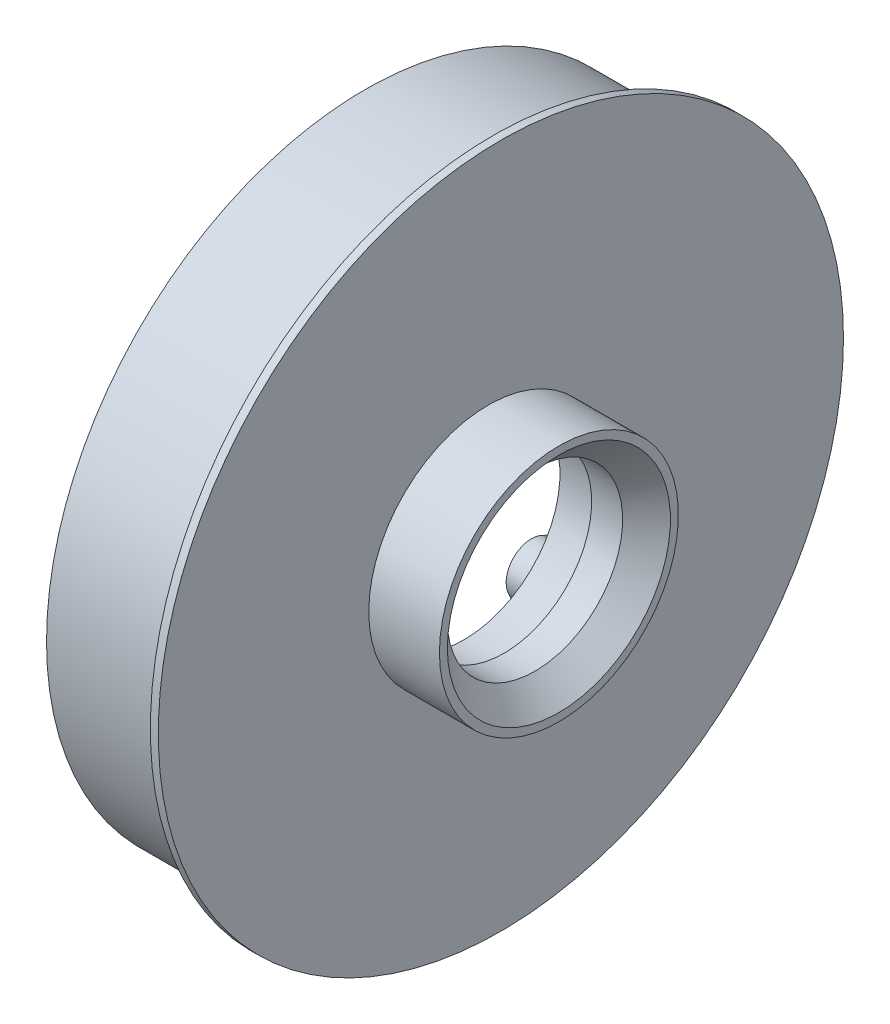
SolidWorks part; units mm, degrees
ref_plane "Front Plane" through (0, 0, 0) normal (0, 0, 1) x (1, 0, 0)
ref_plane "Top Plane" through (0, 0, 0) normal (0, 1, 0) x (1, 0, 0)
ref_plane "Right Plane" through (0, 0, 0) normal (1, 0, 0) x (0, 0, -1)
sketch "Sketch2" plane through (0, 0, 0) normal (0, 0, 1) x (1, 0, 0)
  line L0 (0, 0) -> (58.591, 0) construction
  line L2 (0, 0) -> (18.4, 0)
  line L3 (0, 0) -> (0, 2.5)
  line L4 (0, 2.5) -> (18.4, 2.5)
  line L5 (18.4, 0) -> (18.4, 2.5)
  line L6 (6, 2.5) -> (6, 6)
  line L11 (6, 6) -> (9.97, 6)
  line L16 (12.97, 6) -> (12.97, 3)
  line L17 (12.97, 3) -> (13.6304, 3)
  line L18 (13.6304, 3) -> (13.6304, 2.5)
  line L19 (13.6304, 2.5) -> (6, 2.5)
  line L22 (13.6304, 2.5) -> (16.1104, 2.5)
  line L23 (13.6304, 2.5) -> (13.6304, 4)
  line L24 (13.6304, 4) -> (16.1104, 4)
  line L25 (16.1104, 2.5) -> (16.1104, 4)
  line L27 (6, 6) -> (9.97, 6)
  line L28 (6, 6) -> (6, 9)
  line L29 (6, 9) -> (9.97, 9)
  line L30 (9.97, 6) -> (9.97, 9)
  line L31 (6, 9) -> (6, 8.25)
  line L32 (6, 8.25) -> (5, 8.25)
  line L33 (8.58, 22.001) -> (8.58, 12.476) construction
  line L34 (5, 12.476) -> (12.16, 12.476)
  line L35 (9.97, 9) -> (12.16, 9)
  line L36 (5, 7.5) -> (3, 7.5)
  line L37 (5, 8.25) -> (5, 12.476)
  line L38 (5, 7.5) -> (5, 14)
  line L39 (5, 14) -> (3, 14)
  line L40 (3, 7.5) -> (3, 14)
  line L41 (5, 22.001) -> (12.16, 22.001)
  line L42 (5, 22.001) -> (5, 30.1625)
  line L43 (5, 30.1625) -> (12.16, 30.1625)
  line L44 (12.16, 22.001) -> (12.16, 30.1625)
  line L49 (16.6304, 22.001) -> (16.6304, 7.5)
  line L51 (23.0104, 7.5) -> (23.0104, 6.5)
  line L54 (16.1104, 4) -> (13.6304, 4)
  line L56 (18.0304, 7.5) -> (23.0104, 7.5)
  line L57 (13.16, 22.001) -> (16.6304, 22.001)
  line L58 (16.1104, 3.5) -> (20.0104, 3.5)
  line L59 (29.9004, 14) -> (26.9004, 11)
  line L60 (4, 31.75) -> (18.0304, 31.75)
  line L61 (18.0304, 7.5) -> (23.0104, 7.5)
  line L62 (18.0304, 7.5) -> (18.0304, 12)
  line L63 (18.0304, 12) -> (23.0104, 12)
  line L64 (23.0104, 7.5) -> (23.0104, 12)
  line L65 (18.0304, 31.75) -> (18.0304, 12)
  line L66 (23.0104, 11) -> (26.9004, 11)
  line L67 (34.8004, 23) -> (31.3004, 19.5)
  line L68 (35.8004, 31) -> (38.7904, 33.99)
  line L69 (29.9004, 14) -> (29.9004, 15)
  line L70 (29.9004, 15) -> (22.9304, 15)
  line L71 (22.9304, 15) -> (21.0304, 15)
  line L72 (18.0304, 7.5) -> (16.6304, 7.5)
  line L73 (21.0304, 15) -> (21.0304, 43)
  line L74 (20.0304, 40) -> (10.0704, 40)
  line L75 (10.0704, 40) -> (4, 40)
  line L76 (21.0304, 43) -> (20.0304, 43)
  line L77 (22.9304, 15) -> (29.9004, 15)
  line L78 (22.9304, 15) -> (22.9304, 21)
  line L79 (22.9304, 21) -> (29.9004, 21)
  line L80 (29.9004, 15) -> (29.9004, 21)
  line L81 (10.0704, 40) -> (20.0304, 40)
  line L82 (10.0704, 40) -> (10.0704, 50)
  line L83 (10.0704, 50) -> (20.0304, 50)
  line L84 (20.0304, 40) -> (20.0304, 50)
  line L85 (4, 40) -> (4, 31.75)
  line L86 (12.97, 3) -> (12.97, 2.5)
  line L87 (31.3004, 19.5) -> (29.9004, 19.5)
  line L88 (21.51, 63.5) -> (21.51, 44)
  line L89 (21.51, 63.5) -> (25.9304, 63.5)
  line L90 (25.9304, 63.5) -> (25.9304, 25)
  line L91 (27.8304, 25) -> (25.9304, 25)
  line L92 (10.0704, 48) -> (9, 48)
  line L93 (9, 48) -> (9, 53.476)
  line L94 (9, 53.476) -> (20.0304, 53.476)
  line L95 (20.0304, 53.476) -> (20.0304, 50)
  line L96 (14.5152, 63.001) -> (14.5152, 53.476) construction
  line L97 (9, 63.001) -> (20.0304, 63.001)
  line L98 (9, 63.001) -> (9, 68.2625)
  line L99 (9, 68.2625) -> (20.0304, 68.2625)
  line L100 (20.0304, 63.001) -> (20.0304, 68.2625)
  line L101 (12.97, 6) -> (11.97, 6)
  line L102 (9, 42.5) -> (5, 42.5)
  line L103 (9, 42.5) -> (9, 55)
  line L104 (9, 55) -> (5, 55)
  line L105 (5, 42.5) -> (5, 55)
  line L106 (9.97, 6) -> (10.87, 6)
  line L107 (27.8304, 25) -> (34.8004, 25)
  line L108 (34.8004, 25) -> (34.8004, 23)
  line L109 (0, 0) -> (-2, 0)
  line L110 (0, 0) -> (0, 11)
  line L111 (27.8304, 25) -> (34.8004, 25)
  line L112 (27.8304, 25) -> (27.8304, 32.5)
  line L113 (27.8304, 32.5) -> (34.8004, 32.5)
  line L114 (34.8004, 25) -> (34.8004, 32.5)
  line L115 (35.8004, 31) -> (34.8004, 31)
  line L116 (27.8304, 32.5) -> (27.8304, 64.5)
  line L117 (21.1827, 74.025) -> (6.8477, 74.025)
  line L118 (6.8477, 74.025) -> (6.8477, 76.2)
  line L119 (38.7904, 47.29) -> (30.8304, 55.25)
  line L120 (0, 11) -> (-2, 11)
  line L121 (38.7904, 43.815) -> (30.8529, 43.815)
  line L123 (-4.8, 69.85) -> (1.55, 76.2)
  line L124 (38.7904, 47.29) -> (38.7904, 33.99)
  line L125 (-2, 0) -> (-2, 11)
  line L126 (38.7904, 37.465) -> (30.8529, 37.465)
  line L127 (30.8529, 43.815) -> (30.8529, 37.465)
  line L128 (6, 2.5) -> (6, 0)
  line L129 (0, 63.5) -> (0, 30)
  line L132 (5, 63.5) -> (0, 63.5)
  line L136 (-1.8, 30) -> (-11.76, 30)
  line L138 (-13.76, 25.4) -> (-2, 25.4)
  line L139 (-2, 25.4) -> (-2, 11.5)
  line L140 (27.8304, 64.5) -> (21.1827, 64.5)
  line L141 (-1.8, 30) -> (-11.76, 30)
  line L142 (-1.8, 30) -> (-1.8, 39)
  line L143 (-1.8, 39) -> (-11.76, 39)
  line L144 (-11.76, 30) -> (-11.76, 39)
  line L145 (21.1827, 64.5) -> (21.1827, 74.025)
  line L146 (-12.76, 37) -> (-12.76, 47.29)
  line L147 (-12.76, 37) -> (-11.76, 37)
  line L148 (30.8304, 55.25) -> (30.8304, 76.2)
  line L149 (11.97, 6) -> (11.97, 5.45)
  line L154 (-2, 11.5) -> (1, 11.5)
  line L155 (5, 60.6197) -> (24.05, 60.6197)
  line L160 (5, 60.6197) -> (5, 55.8572)
  line L161 (5, 55.8572) -> (24.05, 55.8572)
  line L166 (24.05, 60.6197) -> (24.05, 55.8572)
  line L167 (5, 60.6197) -> (24.05, 55.8572) construction
  line L172 (5, 55.8572) -> (24.05, 60.6197) construction
  line L173 (24.05, 62.2072) -> (25.9304, 62.2072)
  line L174 (11.97, 5.45) -> (10.87, 5.45)
  line L175 (10.87, 6) -> (10.87, 5.45)
  line L176 (24.05, 62.2072) -> (24.05, 54.2697)
  line L177 (24.05, 54.2697) -> (25.9304, 54.2697)
  line L178 (25.9304, 62.2072) -> (25.9304, 54.2697)
  line L179 (24.05, 62.2072) -> (25.9304, 54.2697) construction
  line L180 (24.05, 54.2697) -> (25.9304, 62.2072) construction
  line L181 (3, 19.6197) -> (15.7, 19.6197)
  line L182 (3, 19.6197) -> (3, 14.8572)
  line L183 (3, 14.8572) -> (15.7, 14.8572)
  line L184 (15.7, 19.6197) -> (15.7, 14.8572)
  line L185 (3, 19.6197) -> (15.7, 14.8572) construction
  line L186 (3, 14.8572) -> (15.7, 19.6197) construction
  line L187 (15.7, 21.2072) -> (16.6304, 21.2072)
  line L188 (15.7, 21.2072) -> (15.7, 13.2697)
  line L189 (15.7, 13.2697) -> (16.6304, 13.2697)
  line L190 (16.6304, 21.2072) -> (16.6304, 13.2697)
  line L191 (15.7, 21.2072) -> (16.6304, 13.2697) construction
  line L192 (15.7, 13.2697) -> (16.6304, 21.2072) construction
  line L193 (1, 11.5) -> (1, 6.5)
  line L194 (1, 6.5) -> (3, 6.5)
  line L195 (23.0104, 6.5) -> (20.0104, 3.5)
  line L196 (5, 63.5) -> (5, 42.5)
  line L197 (5, 42.5) -> (3, 42.5)
  line L198 (3, 42.5) -> (3, 6.5)
  line L199 (6, 0) -> (12.97, 0)
  line L200 (12.97, 0) -> (12.97, 2.5)
  line L201 (18.0304, 31.75) -> (18.0304, 35.875)
  line L202 (18.0304, 35.875) -> (21.0304, 35.875)
  line L203 (30.8304, 76.2) -> (6.8477, 76.2)
  line L204 (3.4027, 69.85) -> (7.8477, 69.85) construction
  line L205 (7.8477, 67.4687) -> (26.8977, 67.4688)
  line L206 (7.8477, 74.025) -> (7.8477, 64.5)
  line L207 (7.8477, 64.5) -> (-1.8, 64.5)
  line L208 (-1.8, 64.5) -> (-1.8, 39)
  line L209 (-12.76, 47.29) -> (-4.8, 55.25)
  line L210 (-4.8, 55.25) -> (-4.8, 69.85)
  line L211 (7.8477, 67.4687) -> (7.8477, 72.2313)
  line L212 (7.8477, 72.2313) -> (26.8977, 72.2313)
  line L213 (26.8977, 67.4688) -> (26.8977, 72.2313)
  line L214 (26.8977, 73.8187) -> (30.8304, 73.8187)
  line L215 (26.8977, 73.8187) -> (26.8977, 65.8813)
  line L216 (26.8977, 65.8813) -> (30.8304, 65.8813)
  line L217 (30.8304, 73.8187) -> (30.8304, 65.8813)
  line L218 (3.4027, 72.2313) -> (25.6277, 72.2313)
  line L219 (3.4027, 72.2313) -> (3.4027, 67.4687)
  line L220 (3.4027, 67.4687) -> (25.6277, 67.4687)
  line L221 (25.6277, 72.2313) -> (25.6277, 67.4687)
  line L222 (25.6277, 69.85) -> (21.1827, 69.85) construction
  line L223 (21.51, 44) -> (22.9304, 44)
  line L224 (22.9304, 44) -> (22.9304, 21)
  line L225 (13.6304, 4) -> (13.6304, 12.2697)
  line L226 (13.6304, 12.2697) -> (13.16, 12.2697)
  line L227 (13.16, 12.2697) -> (13.16, 22.001)
  line L228 (12.16, 9) -> (12.16, 12.476)
  line L229 (-1.8, 30) -> (0, 30)
  line L230 (9, 65.6317) -> (3.4027, 65.6317) construction
  line L231 (20.0304, 65.6317) -> (25.6277, 65.6317) construction
  line L232 (1.55, 76.2) -> (6.8477, 76.2)
  line L233 (-11.76, 30) -> (-13.76, 30)
  line L234 (-13.76, 30) -> (-13.76, 25.4)
  circle A0 centre (26.8804, 25.95) radius 0.95
  circle A1 centre (21.9804, 15.95) radius 0.95
  circle A2 centre (17.3304, 8.2) radius 0.7
  circle A3 centre (10.42, 6.45) radius 0.45
  circle A4 centre (-0.9, 30.9) radius 0.9
  point P7 (24.9902, 58.2385)
  point P131 (16.1652, 17.2385)
  point P135 (14.525, 58.2385)
  point P146 (9.35, 17.2385)
sketch "Sketch3" plane through (0, 0, 0) normal (1, 0, 0) x (0, 0, -1)
  line L0 (0, 0) -> (0, 69.85) construction
  line L1 (0, 0) -> (13.6271, 68.5079) construction
  line L2 (0, 0) -> (0, 58.2385) construction
  line L3 (0, 0) -> (50.436, 29.1192) construction
  line L4 (0, 0) -> (0, 31.75) construction
  line L5 (0, 0) -> (12.1502, 29.3332) construction
  line L6 (0, 0) -> (0, 17.2385) construction
  line L7 (0, 0) -> (14.929, 8.6192) construction
  line L8 (0, 0) -> (0, 58.2385) construction
  line L9 (0, 0) -> (50.436, 29.1192) construction
  line L10 (0, 0) -> (5.9583, 29.9542) construction
  line L11 (0, 0) -> (16.9677, 25.394) construction
  circle A0 centre (0, 0) radius 69.85 construction
  circle A1 centre (0, 0) radius 58.2385 construction
  circle A2 centre (0, 0) radius 31.75 construction
  circle A3 centre (0, 0) radius 17.2385 construction
  circle A4 centre (0, 69.85) radius 3.175
  circle A5 centre (0, 58.2385) radius 4.7625
  circle A6 centre (0, 31.75) radius 3.175
  circle A7 centre (0, 17.2385) radius 4.7625
  circle A8 centre (13.6271, 68.5079) radius 3.175
  circle A9 centre (26.7304, 64.533) radius 3.175
  circle A10 centre (38.8066, 58.0782) radius 3.175
  circle A11 centre (49.3914, 49.3914) radius 3.175
  circle A12 centre (58.0782, 38.8066) radius 3.175
  circle A13 centre (64.533, 26.7304) radius 3.175
  circle A14 centre (68.5079, 13.6271) radius 3.175
  circle A15 centre (69.85, 0) radius 3.175
  circle A16 centre (68.5079, -13.6271) radius 3.175
  circle A17 centre (64.533, -26.7304) radius 3.175
  circle A18 centre (58.0782, -38.8066) radius 3.175
  circle A19 centre (49.3914, -49.3914) radius 3.175
  circle A20 centre (38.8066, -58.0782) radius 3.175
  circle A21 centre (26.7304, -64.533) radius 3.175
  circle A22 centre (13.6271, -68.5079) radius 3.175
  circle A23 centre (0, -69.85) radius 3.175
  circle A24 centre (-13.6271, -68.5079) radius 3.175
  circle A25 centre (-26.7304, -64.533) radius 3.175
  circle A26 centre (-38.8066, -58.0782) radius 3.175
  circle A27 centre (-49.3914, -49.3914) radius 3.175
  circle A28 centre (-58.0782, -38.8066) radius 3.175
  circle A29 centre (-64.533, -26.7304) radius 3.175
  circle A30 centre (-68.5079, -13.6271) radius 3.175
  circle A31 centre (-69.85, 0) radius 3.175
  circle A32 centre (-68.5079, 13.6271) radius 3.175
  circle A33 centre (-64.533, 26.7304) radius 3.175
  circle A34 centre (-58.0782, 38.8066) radius 3.175
  circle A35 centre (-49.3914, 49.3914) radius 3.175
  circle A36 centre (-38.8066, 58.0782) radius 3.175
  circle A37 centre (-26.7304, 64.533) radius 3.175
  circle A38 centre (-13.6271, 68.5079) radius 3.175
  circle A47 centre (50.436, 29.1192) radius 4.7625
  circle A48 centre (50.436, -29.1192) radius 4.7625
  circle A49 centre (0, -58.2385) radius 4.7625
  circle A50 centre (-50.436, -29.1192) radius 4.7625
  circle A51 centre (-50.436, 29.1192) radius 4.7625
  circle A58 centre (12.1502, 29.3332) radius 3.175
  circle A59 centre (22.4506, 22.4506) radius 3.175
  circle A60 centre (29.3332, 12.1502) radius 3.175
  circle A61 centre (31.75, 0) radius 3.175
  circle A62 centre (29.3332, -12.1502) radius 3.175
  circle A63 centre (22.4506, -22.4506) radius 3.175
  circle A64 centre (12.1502, -29.3332) radius 3.175
  circle A65 centre (0, -31.75) radius 3.175
  circle A66 centre (-12.1502, -29.3332) radius 3.175
  circle A67 centre (-22.4506, -22.4506) radius 3.175
  circle A68 centre (-29.3332, -12.1502) radius 3.175
  circle A69 centre (-31.75, 0) radius 3.175
  circle A70 centre (-29.3332, 12.1502) radius 3.175
  circle A71 centre (-22.4506, 22.4506) radius 3.175
  circle A72 centre (14.929, 8.6192) radius 4.7625
  circle A73 centre (14.929, -8.6192) radius 4.7625
  circle A74 centre (0, -17.2385) radius 4.7625
  circle A75 centre (-14.929, -8.6192) radius 4.7625
  circle A76 centre (-14.929, 8.6192) radius 4.7625
  circle A77 centre (0, 0) radius 50
  circle A78 centre (0, 0) radius 9
  circle A79 centre (-12.1502, 29.3332) radius 3.175
  circle A80 centre (0, 0) radius 76.2
  circle A81 centre (0, 0) radius 74.025
  circle A82 centre (0, 69.85) radius 3.9687
  circle A83 centre (49.3914, 49.3914) radius 3.9687
  circle A84 centre (69.85, 0) radius 3.9688
  circle A85 centre (49.3914, -49.3914) radius 3.9687
  circle A86 centre (0, -69.85) radius 3.9687
  circle A87 centre (-49.3914, -49.3914) radius 3.9687
  circle A88 centre (-69.85, 0) radius 3.9688
  circle A89 centre (-49.3914, 49.3914) radius 3.9687
  circle A90 centre (0, 69.85) radius 2.3812
  circle A91 centre (13.6271, 68.5079) radius 2.3812
  circle A92 centre (26.7304, 64.533) radius 2.3813
  circle A93 centre (38.8066, 58.0782) radius 2.3812
  circle A94 centre (49.3914, 49.3914) radius 2.3812
  circle A95 centre (58.0782, 38.8066) radius 2.3812
  circle A96 centre (64.533, 26.7304) radius 2.3813
  circle A97 centre (68.5079, 13.6271) radius 2.3813
  circle A98 centre (69.85, 0) radius 2.3813
  circle A99 centre (68.5079, -13.6271) radius 2.3813
  circle A100 centre (64.533, -26.7304) radius 2.3813
  circle A101 centre (58.0782, -38.8066) radius 2.3812
  circle A102 centre (49.3914, -49.3914) radius 2.3812
  circle A103 centre (38.8066, -58.0782) radius 2.3812
  circle A104 centre (26.7304, -64.533) radius 2.3813
  circle A105 centre (13.6271, -68.5079) radius 2.3812
  circle A106 centre (0, -69.85) radius 2.3812
  circle A107 centre (-13.6271, -68.5079) radius 2.3812
  circle A108 centre (-26.7304, -64.533) radius 2.3813
  circle A109 centre (-38.8066, -58.0782) radius 2.3812
  circle A110 centre (-49.3914, -49.3914) radius 2.3812
  circle A111 centre (-58.0782, -38.8066) radius 2.3812
  circle A112 centre (-64.533, -26.7304) radius 2.3812
  arc A113 (3.0399, 30.8338) -> (8.9911, 29.65) centre (5.9583, 29.9542) cw
  arc A114 (14.6081, 27.3234) -> (19.6532, 23.9523) centre (16.9677, 25.394) cw
  arc A115 (23.9523, 19.6532) -> (27.3234, 14.6081) centre (25.394, 16.9677) cw
  arc A116 (29.65, 8.9911) -> (30.8338, 3.0399) centre (29.9542, 5.9583) cw
  arc A117 (30.8338, -3.0399) -> (29.65, -8.9911) centre (29.9542, -5.9583) cw
  arc A118 (27.3234, -14.6081) -> (23.9523, -19.6532) centre (25.394, -16.9677) cw
  arc A119 (19.6532, -23.9523) -> (14.6081, -27.3234) centre (16.9677, -25.394) cw
  arc A120 (8.9911, -29.65) -> (3.0399, -30.8338) centre (5.9583, -29.9542) cw
  arc A121 (-3.0399, -30.8338) -> (-8.9911, -29.65) centre (-5.9583, -29.9542) cw
  arc A122 (-14.6081, -27.3234) -> (-19.6532, -23.9523) centre (-16.9677, -25.394) cw
  arc A123 (-23.9523, -19.6532) -> (-27.3234, -14.6081) centre (-25.394, -16.9677) cw
  arc A124 (-29.65, -8.9911) -> (-30.8338, -3.0399) centre (-29.9542, -5.9583) cw
  arc A125 (-30.8338, 3.0399) -> (-29.65, 8.9911) centre (-29.9542, 5.9583) cw
  arc A126 (-27.3234, 14.6081) -> (-23.9523, 19.6532) centre (-25.394, 16.9677) cw
  arc A127 (-19.6532, 23.9523) -> (-14.6081, 27.3234) centre (-16.9677, 25.394) cw
  arc A128 (-8.9911, 29.65) -> (-3.0399, 30.8338) centre (-5.9583, 29.9542) cw
  arc A129 (26.9875, 0) -> (26.9932, 0.1932) centre (30.2705, 0) cw
  arc A130 (65.0988, 0.2771) -> (65.0875, 0) centre (68.4964, 0) ccw
  circle A131 centre (1.5875, 0) radius 40
  circle A132 centre (1.5875, 0) radius 2.5
  circle A133 centre (1.5875, 0) radius 3
  circle A134 centre (1.5875, 0) radius 43
  circle A135 centre (-68.5079, -13.6271) radius 2.3813
  circle A136 centre (-69.85, 0) radius 2.3813
  circle A137 centre (-68.5079, 13.6271) radius 2.3813
  circle A138 centre (-64.533, 26.7304) radius 2.3812
  circle A139 centre (-58.0782, 38.8066) radius 2.3812
  circle A140 centre (-49.3914, 49.3914) radius 2.3812
  circle A141 centre (-38.8066, 58.0782) radius 2.3812
  circle A142 centre (-26.7304, 64.533) radius 2.3813
  circle A143 centre (-13.6271, 68.5079) radius 2.3812
  circle A144 centre (0, 58.2385) radius 2.3812
  circle A145 centre (0, 58.2385) radius 3.9688
  circle A146 centre (50.436, 29.1192) radius 3.9688
  circle A147 centre (50.436, 29.1192) radius 2.3813
  circle A148 centre (50.436, -29.1192) radius 3.9687
  circle A149 centre (50.436, -29.1192) radius 2.3812
  circle A150 centre (0, -58.2385) radius 3.9687
  circle A151 centre (0, -58.2385) radius 2.3812
  circle A152 centre (-50.436, -29.1192) radius 3.9687
  circle A153 centre (-50.436, -29.1192) radius 2.3812
  circle A154 centre (-50.436, 29.1192) radius 3.9687
  circle A155 centre (-50.436, 29.1192) radius 2.3812
  spline S1 degree 4 number of poles 499 (26.9875, 0) -> (26.9932, 0.1932)
  spline S3 degree 4 number of poles 617 (65.0875, 0) -> (65.0988, 0.2771)
  point P116 (0, 0)
  point P225 (0, 0)
sketch "Sketch5" plane through (0, 0, 0) normal (0, 0, 1) x (1, 0, 0)
  line L0 (23.0104, 7.5) -> (23.0104, 12) construction
  line L2 (22.9304, 15) -> (21.0304, 15) construction
  line L3 (29.9004, 14) -> (29.9004, 15) construction
  line L4 (29.9004, 15) -> (22.9304, 15) construction
  line L5 (29.9004, 14) -> (26.9004, 11) construction
  line L6 (23.0104, 11) -> (26.9004, 11) construction
  line L7 (18.0304, 12) -> (23.0104, 12) construction
  line L8 (18.0304, 31.75) -> (18.0304, 12) construction
  line L10 (18.0304, 35.875) -> (21.0304, 35.875) construction
  line L11 (18.0304, 31.75) -> (18.0304, 35.875) construction
  line L12 (23.0104, 11) -> (23.0104, 12)
  line L14 (22.9304, 15) -> (21.0304, 15)
  line L15 (29.9004, 14) -> (29.9004, 15)
  line L16 (29.9004, 15) -> (22.9304, 15)
  line L17 (29.9004, 14) -> (26.9004, 11)
  line L18 (23.0104, 11) -> (26.9004, 11)
  line L19 (18.0304, 12) -> (23.0104, 12)
  line L20 (18.0304, 31.75) -> (18.0304, 12)
  line L22 (18.0304, 35.875) -> (21.0304, 35.875)
  line L23 (18.0304, 31.75) -> (18.0304, 35.875)
  line L24 (21.0304, 15) -> (21.0304, 43) construction
  line L25 (21.0304, 15) -> (21.0304, 35.875)
revolve "Revolve1" add sketch "Sketch5" angle 360 about L0
sketch "Sketch6" plane through (0, 0, 0) normal (1, 0, 0) x (0, 0, -1)
  arc A0 (19.6532, 23.9523) -> (14.6081, 27.3234) centre (16.9677, 25.394) ccw construction
  circle A1 centre (12.1502, 29.3332) radius 3.175 construction
  arc A2 (8.9911, 29.65) -> (3.0399, 30.8338) centre (5.9583, 29.9542) ccw construction
  circle A3 centre (0, 31.75) radius 3.175 construction
  arc A4 (-3.0399, 30.8338) -> (-8.9911, 29.65) centre (-5.9583, 29.9542) ccw construction
  circle A5 centre (22.4506, 22.4506) radius 3.175 construction
  arc A6 (27.3234, 14.6081) -> (23.9523, 19.6532) centre (25.394, 16.9677) ccw construction
  circle A7 centre (29.3332, 12.1502) radius 3.175 construction
  arc A8 (30.8338, 3.0399) -> (29.65, 8.9911) centre (29.9542, 5.9583) ccw construction
  circle A9 centre (31.75, 0) radius 3.175 construction
  arc A10 (29.65, -8.9911) -> (30.8338, -3.0399) centre (29.9542, -5.9583) ccw construction
  circle A11 centre (29.3332, -12.1502) radius 3.175 construction
  arc A12 (23.9523, -19.6532) -> (27.3234, -14.6081) centre (25.394, -16.9677) ccw construction
  circle A13 centre (22.4506, -22.4506) radius 3.175 construction
  arc A14 (14.6081, -27.3234) -> (19.6532, -23.9523) centre (16.9677, -25.394) ccw construction
  circle A15 centre (12.1502, -29.3332) radius 3.175 construction
  arc A16 (3.0399, -30.8338) -> (8.9911, -29.65) centre (5.9583, -29.9542) ccw construction
  circle A17 centre (0, -31.75) radius 3.175 construction
  arc A18 (-8.9911, -29.65) -> (-3.0399, -30.8338) centre (-5.9583, -29.9542) ccw construction
  circle A19 centre (-12.1502, -29.3332) radius 3.175 construction
  arc A20 (-19.6532, -23.9523) -> (-14.6081, -27.3234) centre (-16.9677, -25.394) ccw construction
  circle A21 centre (-22.4506, -22.4506) radius 3.175 construction
  arc A22 (-27.3234, -14.6081) -> (-23.9523, -19.6532) centre (-25.394, -16.9677) ccw construction
  circle A23 centre (-29.3332, -12.1502) radius 3.175 construction
  arc A24 (-30.8338, -3.0399) -> (-29.65, -8.9911) centre (-29.9542, -5.9583) ccw construction
  circle A25 centre (-31.75, 0) radius 3.175 construction
  arc A26 (-29.65, 8.9911) -> (-30.8338, 3.0399) centre (-29.9542, 5.9583) ccw construction
  circle A27 centre (-29.3332, 12.1502) radius 3.175 construction
  arc A28 (-23.9523, 19.6532) -> (-27.3234, 14.6081) centre (-25.394, 16.9677) ccw construction
  circle A29 centre (-12.1502, 29.3332) radius 3.175 construction
  arc A30 (-14.6081, 27.3234) -> (-19.6532, 23.9523) centre (-16.9677, 25.394) ccw construction
  circle A31 centre (-22.4506, 22.4506) radius 3.175 construction
  circle A32 centre (1.5875, 0) radius 43 construction
  arc A33 (19.6532, 23.9523) -> (14.6081, 27.3234) centre (16.9677, 25.394) ccw
  arc A34 (8.9911, 29.65) -> (14.6081, 27.3234) centre (12.1502, 29.3332) ccw
  arc A35 (8.9911, 29.65) -> (3.0399, 30.8338) centre (5.9583, 29.9542) ccw
  arc A36 (-3.0399, 30.8338) -> (3.0399, 30.8338) centre (0, 31.75) ccw
  arc A37 (-3.0399, 30.8338) -> (-8.9911, 29.65) centre (-5.9583, 29.9542) ccw
  arc A38 (19.6532, 23.9523) -> (23.9523, 19.6532) centre (22.4506, 22.4506) ccw
  arc A39 (27.3234, 14.6081) -> (23.9523, 19.6532) centre (25.394, 16.9677) ccw
  arc A40 (27.3234, 14.6081) -> (29.65, 8.9911) centre (29.3332, 12.1502) ccw
  arc A41 (30.8338, 3.0399) -> (29.65, 8.9911) centre (29.9542, 5.9583) ccw
  arc A42 (30.8338, 3.0399) -> (30.8338, -3.0399) centre (31.75, 0) ccw
  arc A43 (29.65, -8.9911) -> (30.8338, -3.0399) centre (29.9542, -5.9583) ccw
  arc A44 (29.65, -8.9911) -> (27.3234, -14.6081) centre (29.3332, -12.1502) ccw
  arc A45 (23.9523, -19.6532) -> (27.3234, -14.6081) centre (25.394, -16.9677) ccw
  arc A46 (23.9523, -19.6532) -> (19.6532, -23.9523) centre (22.4506, -22.4506) ccw
  arc A47 (14.6081, -27.3234) -> (19.6532, -23.9523) centre (16.9677, -25.394) ccw
  arc A48 (14.6081, -27.3234) -> (8.9911, -29.65) centre (12.1502, -29.3332) ccw
  arc A49 (3.0399, -30.8338) -> (8.9911, -29.65) centre (5.9583, -29.9542) ccw
  arc A50 (3.0399, -30.8338) -> (-3.0399, -30.8338) centre (0, -31.75) ccw
  arc A51 (-8.9911, -29.65) -> (-3.0399, -30.8338) centre (-5.9583, -29.9542) ccw
  arc A52 (-8.9911, -29.65) -> (-14.6081, -27.3234) centre (-12.1502, -29.3332) ccw
  arc A53 (-19.6532, -23.9523) -> (-14.6081, -27.3234) centre (-16.9677, -25.394) ccw
  arc A54 (-19.6532, -23.9523) -> (-23.9523, -19.6532) centre (-22.4506, -22.4506) ccw
  arc A55 (-27.3234, -14.6081) -> (-23.9523, -19.6532) centre (-25.394, -16.9677) ccw
  arc A56 (-27.3234, -14.6081) -> (-29.65, -8.9911) centre (-29.3332, -12.1502) ccw
  arc A57 (-30.8338, -3.0399) -> (-29.65, -8.9911) centre (-29.9542, -5.9583) ccw
  arc A58 (-30.8338, -3.0399) -> (-30.8338, 3.0399) centre (-31.75, 0) ccw
  arc A59 (-29.65, 8.9911) -> (-30.8338, 3.0399) centre (-29.9542, 5.9583) ccw
  arc A60 (-29.65, 8.9911) -> (-27.3234, 14.6081) centre (-29.3332, 12.1502) ccw
  arc A61 (-23.9523, 19.6532) -> (-27.3234, 14.6081) centre (-25.394, 16.9677) ccw
  arc A62 (-14.6081, 27.3234) -> (-8.9911, 29.65) centre (-12.1502, 29.3332) ccw
  arc A63 (-14.6081, 27.3234) -> (-19.6532, 23.9523) centre (-16.9677, 25.394) ccw
  arc A64 (-23.9523, 19.6532) -> (-19.6532, 23.9523) centre (-22.4506, 22.4506) ccw
  circle A65 centre (1.5875, 0) radius 43
extrude "Boss-Extrude1" add sketch "Sketch6" along normal up to vertex (21.0304 mm away) from vertex contours A65 A61 A64 A63 A62 A37 A36 A35 A34 A33 A38 A39 A40 A41 A42 A43 A44 A45 A46 A47 A48 A49 A50 A51 A52 A53 A54 A55 A56 A57 A58 A59 A60 region at (0, 0, 40.1963) up to point (21.0304, 43, 0) starting at point (4, 40, 0)
sketch "Sketch7" plane through (0, 0, 0) normal (1, 0, 0) x (0, 0, -1)
  circle A0 centre (1.5875, 0) radius 43 construction
  circle A1 centre (1.5875, 0) radius 40 construction
  circle A2 centre (1.5875, 0) radius 43
  circle A3 centre (1.5875, 0) radius 40
extrude "Cut-Extrude1" cut sketch "Sketch7" along normal up to vertex (20.0304 mm away) up to point (20.0304, 40, 0)
